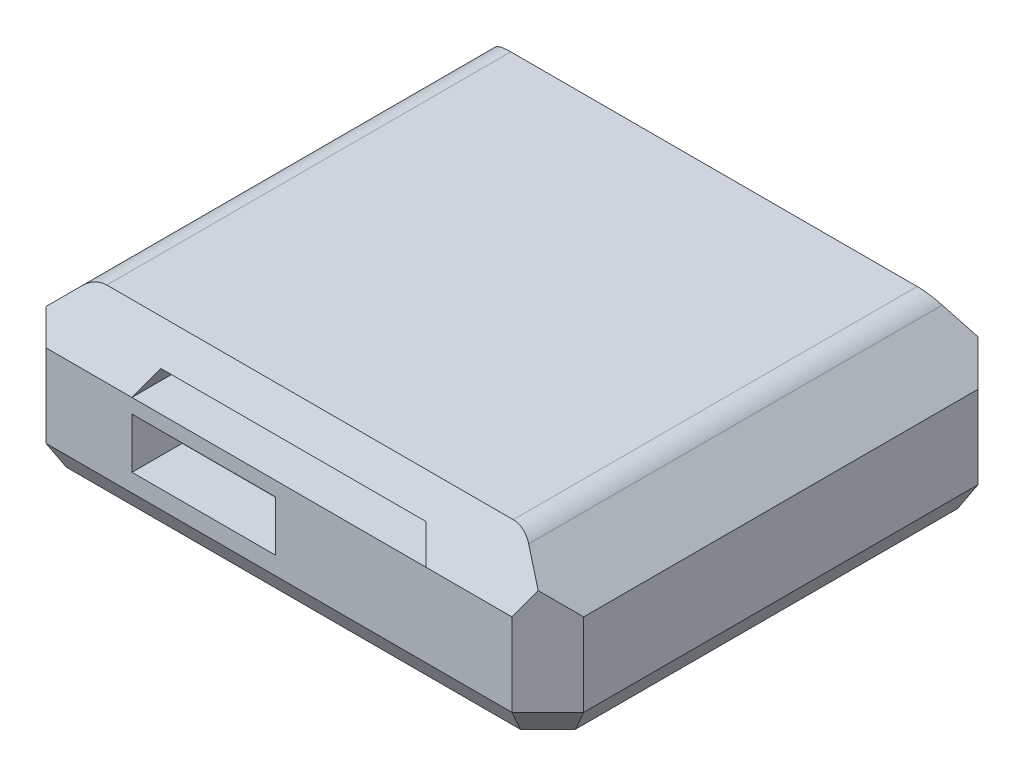
SolidWorks part; units mm, degrees
ref_plane "Front Plane" through (0, 0, 0) normal (0, 0, 1) x (1, 0, 0)
ref_plane "Top Plane" through (0, 0, 0) normal (0, 1, 0) x (1, 0, 0)
ref_plane "Right Plane" through (0, 0, 0) normal (1, 0, 0) x (0, 0, -1)
sketch "Sketch2" plane through (0, 0, 0) normal (0, 1, 0) x (1, 0, 0)
  line L1 (37.5, -32.5) -> (-37.5, -32.5)
  line L2 (37.5, -32.5) -> (37.5, 32.5)
  line L3 (37.5, 32.5) -> (-37.5, 32.5)
  line L4 (-37.5, -32.5) -> (-37.5, 32.5)
  line L5 (37.5, -32.5) -> (-37.5, 32.5) construction
  line L6 (37.5, 32.5) -> (-37.5, -32.5) construction
  point P0 (0, 0)
  dimension "D1" = 65
  dimension "D2" = 75
extrude "Boss-Extrude1" add sketch "Sketch2" along normal blind 15
sketch "Sketch4" plane through (0, 0, 32.5) normal (0, 0, 1) x (1, 0, 0)
  line L0 (-37.5, 15) -> (-30, 22.5)
  line L1 (-37.5, 15) -> (-37.5, 0) construction
  line L2 (-30, 22.5) -> (30, 22.5)
  line L3 (30, 22.5) -> (37.5, 15)
  line L4 (-20.5207, 15) -> (-18.5, 18.5)
  line L5 (-37.5, 15) -> (37.5, 15) construction
  line L6 (-18.5, 18.5) -> (18.5, 18.5)
  line L7 (18.5, 18.5) -> (20.5207, 15)
  line L8 (20.5207, 15) -> (37.5, 15)
  line L9 (0, 0) -> (0, 18.5) construction
  line L10 (-20.5207, 15) -> (-37.5, 15)
  line L11 (37.5, 15) -> (20.5207, 15)
  line M11 (37.5, 15) -> (-37.5, 15)
  dimension "D1" = 4
  dimension "D2" = 60
  dimension "D3" = 60
  dimension "D4" = 45
  dimension "D5" = 45
  dimension "D6" = 37
  dimension "D7" = 3.5
extrude "Boss-Extrude3" add sketch "Sketch4" against normal offset from surface (55 mm away) 5 from offset 5 contours L6 L7 L3 L2 L0 L4 M11 region at (0, 19.3098, 32.5) up to face at (0, 7.5, -32.5) offset against normal yes
chamfer "Chamfer1" distance 5 angle 60 1 edges at (-29.0104, 15, -27.5) first distance on face at (0, 15, 0)
chamfer "Chamfer2" distance 5 angle 60 1 edges at (-29.0104, 15, 27.5) first distance on face at (0, 15, 13.75)
fillet "Fillet3" radius 4 2 edges at (30, 22.5, 0) (-30, 22.5, 0)
sketch "Sketch5" plane through (0, 0, 0) normal (0, -1, 0) x (1, 0, 0)
  line L0 (-32.5, 0) -> (0, 0) construction
  line L1 (-32.5, 25.5) -> (18.5, 25.5)
  line L2 (-32.5, 25.5) -> (-32.5, -25.5)
  line L3 (-32.5, -25.5) -> (18.5, -25.5)
  line L4 (18.5, 25.5) -> (18.5, -25.5)
  line L5 (-37.5, -32.5) -> (-37.5, 32.5) construction
  dimension "D1" = 51
  dimension "D2" = 51
  dimension "D3" = 5
extrude "Cut-Extrude2" cut sketch "Sketch5" against normal offset from surface (13 mm away) 2 up to face at (0, 15, 0)
chamfer "Chamfer3" distance 5 angle 45 4 edges at (37.5, 7.5, 32.5) (-37.5, 7.5, 32.5) (-37.5, 7.5, -32.5) (37.5, 7.5, -32.5)
fillet "Fillet4" radius 4 4 edges at (18.5, 6.5, -25.5) (18.5, 6.5, 25.5) (-32.5, 6.5, -25.5) (-32.5, 6.5, 25.5)
sketch "Sketch7" plane through (0, 0, 0) normal (0, -1, 0) x (1, 0, 0)
  line L0 (272.4934, 284.4269) -> (1283.1601, 284.4269) construction
  line L1 (27.4, 12.2337) -> (21.4298, 3.8639)
  line L2 (21.4298, 3.8639) -> (27.4, 5.9196)
  line L3 (27.4, 5.9196) -> (27.4, 12.2337)
  line L4 (21.4065, 3.6443) -> (27.4, 5.708)
  line L5 (27.4, 5.708) -> (27.4, 0.5904)
  line L6 (27.4, 0.5904) -> (21.4065, 3.6443)
  line L7 (21.5223, 2.2385) -> (27.4, -0.7564)
  line L8 (27.4, -0.7564) -> (27.4, -4.7663)
  line L9 (27.4, -4.7663) -> (21.5223, 2.2385)
  line L10 (27.5, 12.1803) -> (27.5, -2.7601) construction
  line L11 (27.6, 5.708) -> (27.6, 0.5904)
  line L12 (27.6, -0.7564) -> (27.6, -4.7663)
  line L13 (27.6, -4.7663) -> (33.4777, 2.2385)
  line L14 (33.4777, 2.2385) -> (27.6, -0.7564)
  line L15 (27.6, 0.5904) -> (33.5935, 3.6443)
  line L16 (33.5935, 3.6443) -> (27.6, 5.708)
  line L17 (33.5702, 3.8639) -> (27.6, 5.9196)
  line L18 (27.6, 12.2337) -> (33.5702, 3.8639)
  line L19 (27.6, 5.9196) -> (27.6, 12.2337)
  line L20 (18.5, 21.5) -> (37.5, 21.5) construction
  line L21 (37.5, 27.5) -> (37.5, -27.5) construction
  line L22 (18.5, -21.5) -> (18.5, 21.5) construction
  dimension "D1" = 109
  dimension "D2" = 35.5
  dimension "D3" = 117
  dimension "D4" = 40
  dimension "D5" = 0.2
  dimension "D6" = 1.2
  dimension "D7" = 17
  dimension "D8" = 0.1
  dimension "D9" = 9
extrude "Cut-Extrude3" cut sketch "Sketch7" against normal blind 1
sketch "Sketch9" plane through (0, 0, 0) normal (0, -1, 0) x (1, 0, 0)
  line L0 (22, -12) -> (22, -9) construction
  line L1 (20.5, -12) -> (20.5, -9)
  line L2 (23.5, -12) -> (23.5, -9)
  line L3 (22, -20) -> (22, -17) construction
  line L4 (20.5, -20) -> (20.5, -17)
  line L5 (23.5, -20) -> (23.5, -17)
  line L6 (18.5, -21.5) -> (18.5, 21.5) construction
  line L7 (32.5, -32.5) -> (-32.5, -32.5) construction
  arc A0 (20.5, -12) -> (23.5, -12) centre (22, -12) ccw
  arc A1 (23.5, -9) -> (20.5, -9) centre (22, -9) ccw
  arc A2 (20.5, -20) -> (23.5, -20) centre (22, -20) ccw
  arc A3 (23.5, -17) -> (20.5, -17) centre (22, -17) ccw
  point P2 (22, -10.5)
  point P7 (22, -18.5)
  dimension "D3" = 1.5
  dimension "D1" = 3
  dimension "D2" = 3
  dimension "D4" = 8
  dimension "D5" = 3.5
  dimension "D6" = 14
extrude "Boss-Extrude4" add sketch "Sketch9" along normal blind 2
chamfer "Chamfer5" distance 0.8 angle 45 8 edges at (20.5, -2, -10.5) (22, -2, -13.5) (22, -2, -7.5) (23.5, -2, -10.5) (20.5, -2, -18.5) (22, -2, -21.5) (22, -2, -15.5) (23.5, -2, -18.5)
chamfer "Chamfer6" distance 2 angle 60 8 edges at (35, 0, -30) (0, 0, -32.5) (-35, 0, -30) (-37.5, 0, 0) (-35, 0, 30) (0, 0, 32.5) (35, 0, 30) (37.5, 0, 0) first distance on face at (22, 0, -10.5)
sketch "Sketch10" plane through (0, 0, 32.5) normal (0, 0, 1) x (1, 0, 0)
  line L1 (-20.5, 13) -> (-0.5, 13)
  line L2 (-20.5, 13) -> (-20.5, 5.9641)
  line L3 (-20.5, 5.9641) -> (-0.5, 5.9641)
  line L4 (-0.5, 13) -> (-0.5, 5.9641)
  line L5 (-32.5, 3.4641) -> (32.5, 3.4641) construction
  line L6 (-32.5, 15) -> (-32.5, 3.4641) construction
  line L7 (-28.5, 13) -> (14.5, 13) construction
  dimension "D2" = 2.5
  dimension "D3" = 20
  dimension "D4" = 12
extrude "Cut-Extrude4" cut sketch "Sketch10" against normal up to next
